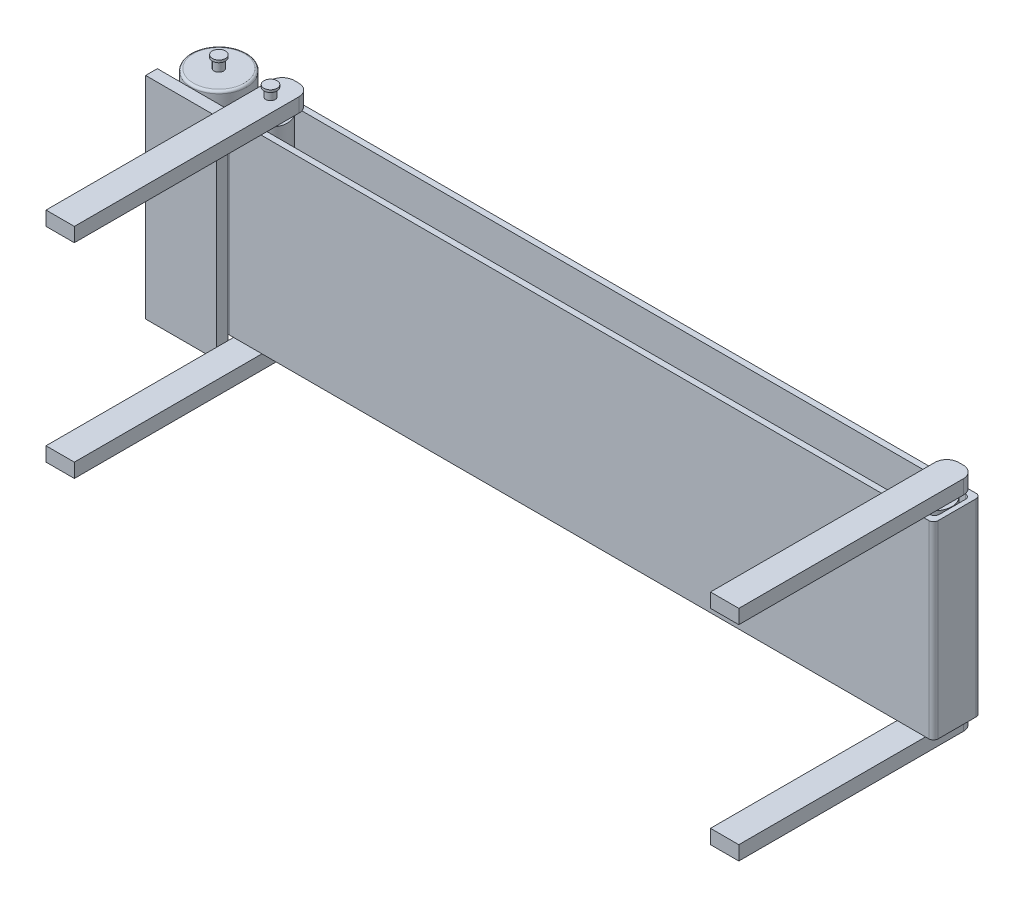
SolidWorks part; units mm, degrees
ref_plane "Alzado" through (0, 0, 0) normal (0, 0, 1) x (1, 0, 0)
ref_plane "Planta" through (0, 0, 0) normal (0, 1, 0) x (1, 0, 0)
ref_plane "Vista lateral" through (0, 0, 0) normal (1, 0, 0) x (0, 0, -1)
sketch "Croquis1" plane through (0, 0, 0) normal (0, 1, 0) x (1, 0, 0)
  line L1 (-74, -5) -> (74, -5)
  line L2 (-75, -4) -> (-75, 4)
  line L3 (-74, 5) -> (74, 5)
  line L4 (75, -4) -> (75, 4)
  line L5 (-75, -5) -> (75, 5) construction
  line L6 (-75, 5) -> (75, -5) construction
  arc A0 (-75, 4) -> (-74, 5) centre (-74, 4) cw
  arc A1 (-74, -5) -> (-75, -4) centre (-74, -4) cw
  arc A2 (74, -5) -> (75, -4) centre (74, -4) ccw
  arc A3 (74, 5) -> (75, 4) centre (74, 4) cw
  point P0 (0, 0)
  dimension "D3" = 1
  dimension "D1" = 150
  dimension "D2" = 10
extrude "Saliente-Extruir1" add sketch "Croquis1" along normal blind 40
sketch "Croquis2" plane through (0, 0, 0) normal (0, -1, 0) x (1, 0, 0)
sketch "Croquis4" plane through (0, 0, 0) normal (0, -1, 0) x (1, 0, 0)
sketch "Croquis5" plane through (0, 0, 0) normal (0, 1, 0) x (1, 0, 0)
  line L1 (73, -3.75) -> (-73, -3.75)
  line L2 (74, -2.75) -> (74, 2.75)
  line L3 (73, 3.75) -> (-73, 3.75)
  line L4 (-74, -2.75) -> (-74, 2.75)
  line L5 (74, -3.75) -> (-74, 3.75) construction
  line L6 (74, 3.75) -> (-74, -3.75) construction
  arc A0 (-73, -3.75) -> (-74, -2.75) centre (-73, -2.75) cw
  arc A1 (-73, 3.75) -> (-74, 2.75) centre (-73, 2.75) ccw
  arc A2 (73, -3.75) -> (74, -2.75) centre (73, -2.75) ccw
  arc A3 (74, 2.75) -> (73, 3.75) centre (73, 2.75) ccw
  point P0 (0, 0)
  dimension "D3" = 1
  dimension "D1" = 148
  dimension "D2" = 7.5
extrude "Cortar-Extruir5" cut sketch "Croquis5" against normal blind 40 and the other way blind 40
sketch "Croquis6" plane through (0, 0, 0) normal (0, 1, 0) x (1, 0, 0)
  line L0 (74, -2.75) -> (74, 2.75) construction
  circle A0 centre (70.3, 0) radius 3.6
  point P4 (74, 0)
  dimension "D1" = 3.7
  dimension "D2" = 7.2
extrude "Saliente-Extruir2" add sketch "Croquis6" along normal blind 40 separate body
sketch "Croquis7" plane through (0, 0, 0) normal (0, -1, 0) x (-1, 0, 0)
  circle A0 centre (-70.3, 0) radius 1.0043
extrude "Saliente-Extruir3" add sketch "Croquis7" along normal blind 0.2 and the other way blind 40.3
sketch "Croquis8" plane through (0, 0, 0) normal (0, 1, 0) x (1, 0, 0)
  line L0 (-74, 2.75) -> (-74, -2.75) construction
  circle A0 centre (-70.3, 0) radius 3.6
  dimension "D1" = 7.2
  dimension "D2" = 3.7
extrude "Saliente-Extruir4" add sketch "Croquis8" along normal blind 40 separate body
sketch "Croquis9" plane through (0, 0, 0) normal (0, -1, 0) x (-1, 0, 0)
  circle A0 centre (70.3065, 0) radius 1
  dimension "D1" = 2
extrude "Saliente-Extruir5" add sketch "Croquis9" along normal blind 0.2 and the other way blind 40.3
ref_plane "Plano1" through (0, -0.2, 0) normal (0, -1, 0) x (-1, 0, 0)
sketch "Croquis11" plane through (0, -0.2, 0) normal (0, -1, 0) x (-1, 0, 0)
  line L2 (67.3065, 0) -> (67.3065, 3)
  line L3 (69.8065, 5.5) -> (70.8065, 5.5)
  line L4 (73.3065, 3) -> (73.3065, 0)
  line L5 (67.3065, 0) -> (67.3065, -44.5)
  line L6 (67.3065, -44.5) -> (73.3065, -44.5)
  line L7 (73.3065, -44.5) -> (73.3065, 0)
  arc A0 (70.8065, 5.5) -> (73.3065, 3) centre (70.8065, 3) cw
  arc A1 (67.3065, 3) -> (69.8065, 5.5) centre (69.8065, 3) cw
  point P12 (67.3065, 5.5)
  dimension "D1" = 2.5
  dimension "D3" = 5.5
  dimension "D4" = 44.5
extrude "Saliente-Extruir7" add sketch "Croquis11" along normal blind 3
sketch "Croquis12" plane through (0, 0, 0) normal (0, -1, 0) x (-1, 0, 0)
  line L2 (-73.3, 0) -> (-73.3, 3.0003)
  line L3 (-70.8, 5.5003) -> (-69.8023, 5.5003)
  line L4 (-67.3023, 3.0003) -> (-67.3023, 0)
  line L5 (-67.3023, 0) -> (-67.3023, -44.5021)
  line L6 (-67.3023, -44.5021) -> (-73.3, -44.5021)
  line L7 (-73.3, -44.5021) -> (-73.3, 0)
  arc A0 (-69.8023, 5.5003) -> (-67.3023, 3.0003) centre (-69.8023, 3.0003) cw
  arc A1 (-73.3, 3.0003) -> (-70.8, 5.5003) centre (-70.8, 3.0003) cw
  dimension "D1" = 2.5
extrude "Saliente-Extruir8" add sketch "Croquis12" along normal blind 3
ref_plane "Plano3" through (0, 40.31, 0) normal (0, 1, 0) x (1, 0, 0)
sketch "Croquis13" plane through (0, 40.31, 0) normal (0, 1, 0) x (1, 0, 0)
  line L2 (67.305, 0) -> (67.305, 2.9967)
  line L3 (69.805, 5.4967) -> (70.8009, 5.4967)
  line L4 (73.3009, 2.9966) -> (73.3, -44.5021)
  line L5 (73.3, -44.5021) -> (67.3023, -44.5021)
  line L6 (67.3023, -44.5021) -> (67.305, 0)
  arc A0 (70.8009, 5.4967) -> (73.3009, 2.9966) centre (70.8009, 2.9967) cw
  arc A1 (67.305, 2.9967) -> (69.805, 5.4967) centre (69.805, 2.9967) cw
  dimension "D1" = 2.5
extrude "Saliente-Extruir9" add sketch "Croquis13" along normal blind 3 separate body
sketch "Croquis14" plane through (0, 40, 0) normal (0, 1, 0) x (1, 0, 0)
  line L1 (-73.3017, 0) -> (-73.3017, 3)
  line L2 (-70.8017, 5.5) -> (-69.8002, 5.5)
  line L3 (-67.3002, 2.9997) -> (-67.3065, -44.5)
  line L4 (-67.3065, 3) -> (-67.3065, -44.5) construction
  line L5 (-67.3065, -44.5) -> (-73.3017, -44.5)
  line L6 (-73.3017, -44.5) -> (-73.3017, 0)
  arc A0 (-69.8002, 5.5) -> (-67.3002, 2.9997) centre (-69.8002, 3) cw
  arc A1 (-73.3017, 3) -> (-70.8017, 5.5) centre (-70.8017, 3) cw
  dimension "D1" = 2.5
extrude "Saliente-Extruir10" add sketch "Croquis14" along normal blind 3
sketch "Croquis15" plane through (0, 43, 0) normal (0, 1, 0) x (1, 0, 0)
  circle A0 centre (-70.3, 0) radius 1
  dimension "D1" = 2
extrude "Saliente-Extruir11" add sketch "Croquis15" along normal blind 2
ref_plane "Plano4" through (0, 45.01, 0) normal (0, 1, 0) x (1, 0, 0)
sketch "Croquis16" plane through (0, 45.01, 0) normal (0, 1, 0) x (1, 0, 0)
  circle A0 centre (-70.3, 0) radius 1.3903
extrude "Saliente-Extruir12" add sketch "Croquis16" along normal blind 0.25 and the other way blind 0.25
ref_plane "Plano5" through (-73.3165, 0, 0) normal (-1, 0, 0) x (0, 0, 1)
sketch "Croquis17" plane through (-73.3165, 0, 0) normal (-1, 0, 0) x (0, 0, 1)
  line L5 (8.4093, -2.5316) -> (5.9284, -2.5316)
  line L6 (8.4093, -2.5316) -> (8.4093, 42.1174)
  line L7 (8.4093, 42.1174) -> (5.9284, 42.1174)
  line L8 (5.9284, -2.5316) -> (5.9284, 42.1174)
  point P1 (0, 0)
  point P2 (0, 0)
  point P8 (13.7795, -2.0807)
extrude "Saliente-Extruir13" add sketch "Croquis17" along normal blind 15 separate body
sketch "Croquis18" plane through (0, 45.26, 0) normal (0, 1, 0) x (1, 0, 0)
  circle A0 centre (-81.2223, 0) radius 1.39
  dimension "D1" = 2.78
extrude "Saliente-Extruir14" add sketch "Croquis18" against normal blind 0.5 separate body
sketch "Croquis19" plane through (0, 45.26, 0) normal (0, 1, 0) x (1, 0, 0)
  circle A0 centre (-81.2223, 0) radius 1.0067
extrude "Saliente-Extruir15" add sketch "Croquis19" against normal blind 2.5
ref_plane "Plano6" through (0, 42.75, 0) normal (0, -1, 0) x (-1, 0, 0)
sketch "Croquis20" plane through (0, 42.75, 0) normal (0, -1, 0) x (-1, 0, 0)
  circle A0 centre (81.2223, 0) radius 5.9
  dimension "D1" = 11.8
extrude "Saliente-Extruir17" add sketch "Croquis20" along normal blind 22.5 separate body
fillet "Redondeo2" radius 4 1 edges at (-81.2223, 20.25, -5.9)
fillet "Redondeo4" radius 0.5 1 edges at (-81.2223, 42.75, -5.9)
sketch "Croquis21" plane through (0, 42.75, 0) normal (0, -1, 0) x (-1, 0, 0)
  line L1 (81.2223, 0) -> (81.2223, -0.312)
